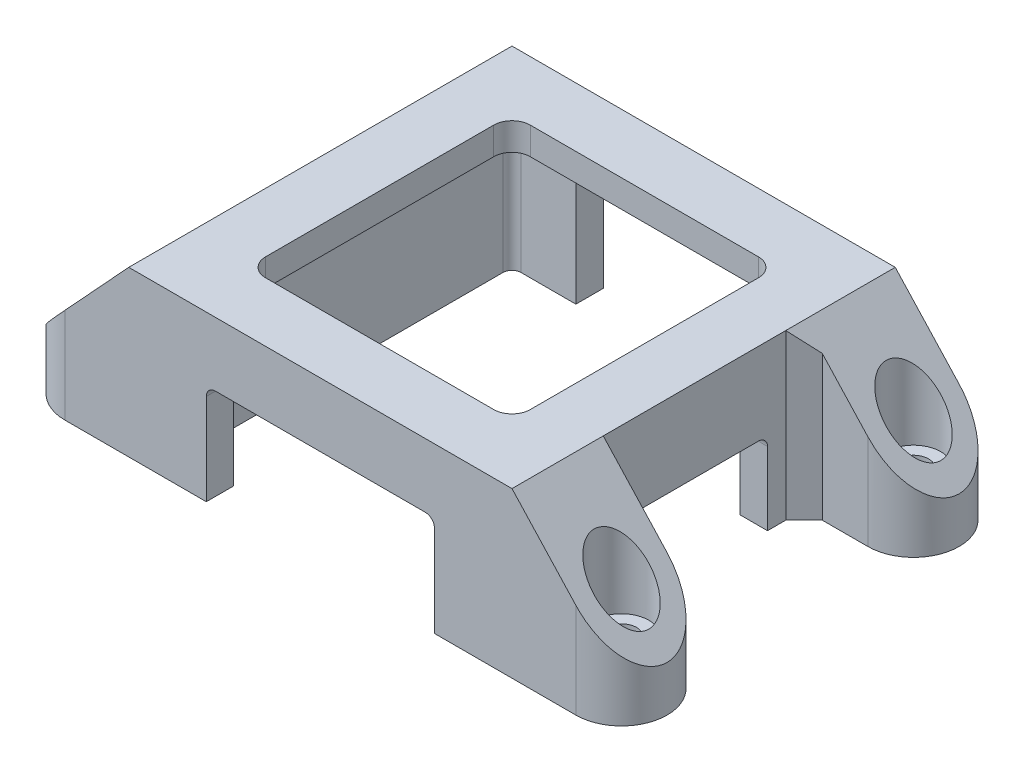
SolidWorks part; units mm, degrees
ref_plane "Front Plane" through (0, 0, 0) normal (0, 0, 1) x (1, 0, 0)
ref_plane "Top Plane" through (0, 0, 0) normal (0, 1, 0) x (1, 0, 0)
ref_plane "Right Plane" through (0, 0, 0) normal (1, 0, 0) x (0, 0, -1)
sketch "Sketch1" plane through (0, 0, 0) normal (0, 1, 0) x (1, 0, 0)
  line L5 (-18, -18) -> (18, -18)
  line L6 (-18, -18) -> (-18, 18)
  line L7 (-18, 18) -> (18, 18)
  line L8 (18, -18) -> (18, 18)
  line L9 (-18, -18) -> (18, 18) construction
  line L10 (-18, 18) -> (18, -18) construction
  point P0 (0, 0)
  dimension "D1" = 36
extrude "Boss-Extrude1" add sketch "Sketch1" along normal blind 15
shell "Shell1" thickness 3 removed face at (0, 0, 0) outward yes
sketch "Sketch2" plane through (0, 0, 21) normal (0, 0, 1) x (1, 0, 0)
  line L1 (-12.5, 0) -> (12.5, 0)
  line L2 (-12.5, 0) -> (-12.5, 11)
  line L3 (-12.5, 11) -> (12.5, 11)
  line L4 (12.5, 0) -> (12.5, 11)
  line L5 (-12.5, 11) -> (12.5, 0) construction
  line L6 (-21, 0) -> (21, 0) construction
  point P6 (0, 5.5)
  dimension "D1" = 11
  dimension "D2" = 25
extrude "Cut-Extrude1" cut sketch "Sketch2" against normal up to next
sketch "Sketch3" plane through (21, 0, 0) normal (1, 0, 0) x (0, 0, -1)
  line L1 (-11, 0) -> (7, 0)
  line L2 (-11, 0) -> (-11, 9)
  line L3 (-11, 9) -> (7, 9)
  line L4 (7, 0) -> (7, 9)
  line L6 (-21, 18) -> (-21, 0) construction
  line L7 (-21, 0) -> (21, 0) construction
  dimension "D1" = 18
  dimension "D2" = 9
  dimension "D3" = 10
extrude "Cut-Extrude2" cut sketch "Sketch3" against normal up to next
sketch "Sketch5" plane through (0, 18, 0) normal (0, 1, 0) x (1, 0, 0)
  line L5 (-14.5, -14.5) -> (14.5, -14.5)
  line L6 (-14.5, -14.5) -> (-14.5, 14.5)
  line L7 (-14.5, 14.5) -> (14.5, 14.5)
  line L8 (14.5, -14.5) -> (14.5, 14.5)
  line L9 (-14.5, -14.5) -> (14.5, 14.5) construction
  line L10 (-14.5, 14.5) -> (14.5, -14.5) construction
  point P3 (0, 0)
  dimension "D1" = 29
extrude "Cut-Extrude3" cut sketch "Sketch5" against normal up to next
fillet "Fillet1" radius 2 4 edges at (-14.5, 16.5, 14.5) (14.5, 16.5, 14.5) (14.5, 16.5, -14.5) (-14.5, 16.5, -14.5)
sketch "Sketch6" plane through (0, 0, -21) normal (0, 0, -1) x (-1, 0, 0)
  line L1 (-11, 0) -> (11, 0)
  line L2 (-11, 0) -> (-11, 14)
  line L3 (-11, 14) -> (11, 14)
  line L4 (11, 0) -> (11, 14)
  line L5 (-11, 14) -> (11, 0) construction
  line L6 (-21, 0) -> (21, 0) construction
  point P6 (0, 7)
  dimension "D1" = 22
  dimension "D2" = 14
extrude "Cut-Extrude4" cut sketch "Sketch6" against normal up to next
fillet "Fillet2" radius 1 6 edges at (-11, 14, -19.5) (11, 14, -19.5) (19.5, 9, -7) (19.5, 9, 11) (12.5, 11, 19.5) (-12.5, 11, 19.5)
sketch "Sketch9" plane through (0, 0, 0) normal (0, -1, 0) x (1, 0, 0)
  line L1 (-21, 21) -> (-33, 21)
  line L2 (-21, 21) -> (-21, 11)
  line L3 (-21, 11) -> (-33, 11)
  line L4 (-33, 21) -> (-33, 11)
  dimension "D1" = 10
  dimension "D2" = 12
extrude "Boss-Extrude3" add sketch "Sketch9" against normal blind 5
sketch "Sketch10" plane through (0, 0, 21) normal (0, 0, 1) x (1, 0, 0)
  line L0 (-21, 18) -> (-33, 5)
  line L1 (-33, 5) -> (-21, 5)
  line L2 (-21, 5) -> (-21, 18)
extrude "Boss-Extrude4" add sketch "Sketch10" against normal up to surface (10 mm away) up to face at (-27, 2.5, 11)
sketch "Sketch11" plane through (0, 0, 0) normal (0, -1, 0) x (1, 0, 0)
  line L0 (-33, 21) -> (-33, 11) construction
  line L1 (-33, 21) -> (-12.5, 21) construction
  circle A0 centre (-28, 16) radius 1.65
  point P4 (-33, 16)
  dimension "D1" = 3.3
  dimension "D2" = 5
  dimension "D3" = 5
extrude "Cut-Extrude5" cut sketch "Sketch11" against normal blind 5
sketch "Sketch12" plane through (0, 5, 0) normal (0, -1, 0) x (1, 0, 0)
  circle A0 centre (-28, 16) radius 3
  dimension "D1" = 6
extrude "Cut-Extrude6" cut sketch "Sketch12" against normal up to next contours A0
sketch "Sketch13" plane through (0, 0, 0) normal (0, -1, 0) x (1, 0, 0)
  circle A0 centre (-28, 16) radius 5
  line M8 (-12.5, 21) -> (-33, 21)
  line M9 (-33, 21) -> (-33, 11)
  line M10 (-33, 11) -> (-21, 11)
  dimension "D1" = 10
extrude "Cut-Extrude7" cut sketch "Sketch13" against normal up to next contours A0 M8 M9 | A0 M9 M10 region at (-31.8832, 0, 19.8832) region at (-31.8832, 0, 12.1168)
mirror "Mirror1" about plane through (0, 0, 0) normal (0, 0, 1) of "Boss-Extrude4", "Boss-Extrude3", "Cut-Extrude7", "Cut-Extrude6", "Cut-Extrude5"
mirror "Mirror3" about plane through (0, 0, 0) normal (1, 0, 0) of "Mirror1"
chamfer "Chamfer1" distance 2 angle 45 3 edges at (21, 9, -11) (-21, 9, 11) (-21, 9, -11)
fillet "Fillet3" radius 1 4 edges at (18, 7.5, -18) (-18, 7.5, 18) (18, 7.5, 18) (-18, 7.5, -18)
